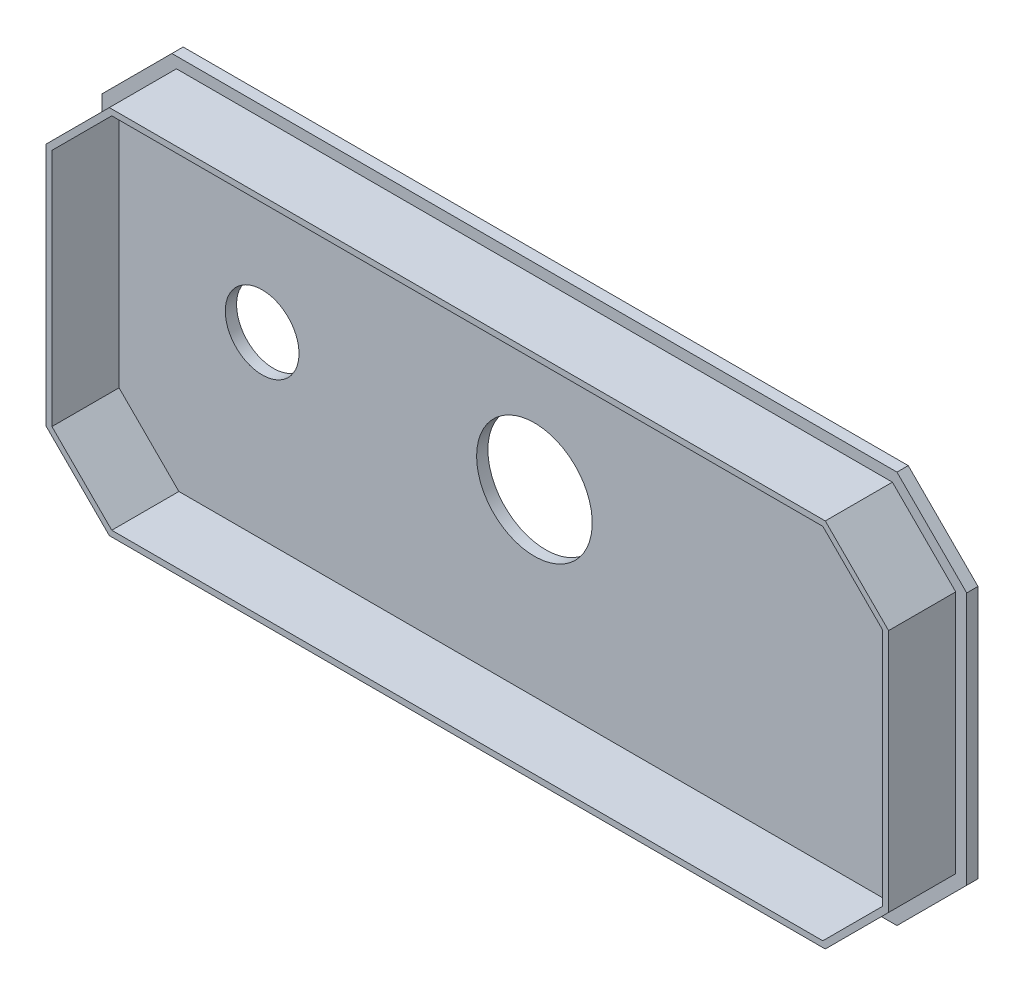
SolidWorks part; units mm, degrees
ref_plane "Front Plane" through (0, 0, 0) normal (0, 0, 1) x (1, 0, 0)
ref_plane "Top Plane" through (0, 0, 0) normal (0, 1, 0) x (1, 0, 0)
ref_plane "Right Plane" through (0, 0, 0) normal (1, 0, 0) x (0, 0, -1)
sketch "Sketch1" plane through (0, 0, 0) normal (0, 0, 1) x (1, 0, 0)
  line L1 (-30.6704, -13.9318) -> (30.6704, -13.9318)
  line L2 (-30.6704, -13.9318) -> (-30.6704, 13.9318)
  line L3 (-30.6704, 13.9318) -> (30.6704, 13.9318)
  line L4 (30.6704, -13.9318) -> (30.6704, 13.9318)
  line L5 (-30.6704, -13.9318) -> (30.6704, 13.9318) construction
  line L6 (-30.6704, 13.9318) -> (30.6704, -13.9318) construction
  point P0 (0, 0)
  dimension "D1" = 61.3408
  dimension "D2" = 27.8636
extrude "Boss-Extrude1" add sketch "Sketch1" along normal blind 0.8
sketch "Sketch2" plane through (0, 0, 0.8) normal (0, 0, 1) x (1, 0, 0)
  line L0 (-30.6704, -8.9821) -> (-25.7207, -13.9318)
  line L1 (-30.6704, 13.9318) -> (-30.6704, -13.9318) construction
  line L2 (-30.6704, 8.9821) -> (-25.7207, 13.9318)
  line L3 (30.6704, 13.9318) -> (-30.6704, 13.9318) construction
  line L4 (-25.7207, 13.9318) -> (-30.6704, 13.9318)
  line L5 (-30.6704, 13.9318) -> (-30.6704, 8.9821)
  line L6 (-30.6704, -13.9318) -> (30.6704, -13.9318) construction
  line L7 (-25.7207, -13.9318) -> (-30.6704, -13.9318)
  line L8 (-30.6704, -13.9318) -> (-30.6704, -8.9821)
  line L9 (25.7207, -13.9318) -> (30.6704, -8.9821)
  line L10 (30.6704, -13.9318) -> (30.6704, 13.9318) construction
  line L11 (30.6704, -8.9821) -> (30.6704, -13.9318)
  line L12 (30.6704, -13.9318) -> (25.7207, -13.9318)
  line L13 (25.7207, 13.9318) -> (30.6704, 8.9821)
  line L14 (30.6704, 8.9821) -> (30.6704, 13.9318)
  line L15 (30.6704, 13.9318) -> (25.7207, 13.9318)
  dimension "D1" = 7
  dimension "D2" = 7
  dimension "D3" = 7
  dimension "D4" = 7
  dimension "D5" = 45
  dimension "D6" = 45
  dimension "D7" = 45
  dimension "D8" = 45
extrude "Cut-Extrude1" cut sketch "Sketch2" against normal through all
sketch "Sketch3" plane through (0, 0, 0.8) normal (0, 0, 1) x (1, 0, 0)
  line L0 (25.3976, 13.1518) -> (-25.3976, 13.1518)
  line L1 (-25.3976, 13.1518) -> (-29.8904, 8.659)
  line L2 (-29.8904, 8.659) -> (-29.8904, -8.659)
  line L3 (-29.8904, -8.659) -> (-25.3976, -13.1518)
  line L4 (-25.3976, -13.1518) -> (25.3976, -13.1518)
  line L5 (25.3976, -13.1518) -> (29.8904, -8.659)
  line L6 (29.8904, -8.659) -> (29.8904, 8.659)
  line L7 (29.8904, 8.659) -> (25.3976, 13.1518)
  line L48 (-25.2236, 12.7318) -> (-29.4704, 8.485)
  line L49 (-29.4704, 8.485) -> (-29.4704, -8.485)
  line L50 (-29.4704, -8.485) -> (-25.2236, -12.7318)
  line L51 (-25.2236, -12.7318) -> (25.2236, -12.7318)
  line L52 (25.2236, -12.7318) -> (29.4704, -8.485)
  line L53 (29.4704, -8.485) -> (29.4704, 8.485)
  line L54 (29.4704, 8.485) -> (25.2236, 12.7318)
  line L55 (25.2236, 12.7318) -> (-25.2236, 12.7318)
  line L56 (-25.2236, 12.7318) -> (-29.4704, 8.485)
  line L57 (-29.4704, 8.485) -> (-29.4704, -8.485)
  line L58 (-29.4704, -8.485) -> (-25.2236, -12.7318)
  line L59 (-25.2236, -12.7318) -> (25.2236, -12.7318)
  line L60 (25.2236, -12.7318) -> (29.4704, -8.485)
  line L61 (29.4704, -8.485) -> (29.4704, 8.485)
  line L62 (29.4704, 8.485) -> (25.2236, 12.7318)
  line L63 (25.2236, 12.7318) -> (-25.2236, 12.7318)
  dimension "D1" = 1.2
  dimension "D2" = 0.42
extrude "Boss-Extrude2" add sketch "Sketch3" along normal blind 4.7625
sketch "Sketch4" plane through (0, 0, 0) normal (0, 0, -1) x (-1, 0, 0)
  line L0 (19.3166, 0) -> (0, 0) construction
  line L1 (30.6704, 8.9821) -> (30.6704, -8.9821) construction
  circle A0 centre (19.3166, 0) radius 2.6162
  dimension "D1" = 5.2324
  dimension "D2" = 11.3538
extrude "Cut-Extrude2" cut sketch "Sketch4" against normal blind 2.54
sketch "Sketch5" plane through (0, 0, 0) normal (0, 0, -1) x (-1, 0, 0)
  circle A0 centre (0, 0) radius 4.1021
  dimension "D1" = 8.2042
extrude "Cut-Extrude3" cut sketch "Sketch5" against normal blind 2.54
